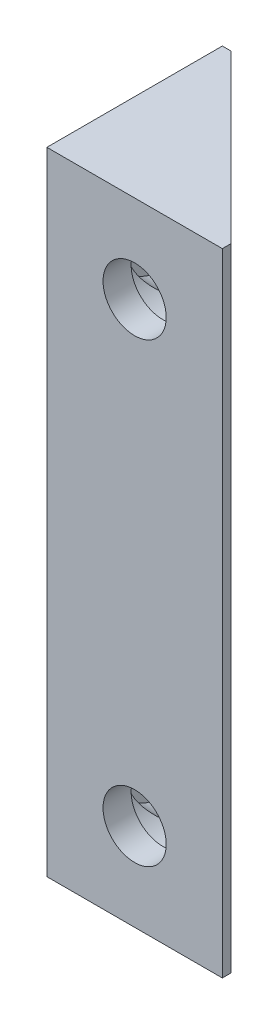
SolidWorks part; units mm, degrees
ref_plane "Front Plane" through (0, 0, 0) normal (0, 0, 1) x (1, 0, 0)
ref_plane "Top Plane" through (0, 0, 0) normal (0, 1, 0) x (1, 0, 0)
ref_plane "Right Plane" through (0, 0, 0) normal (1, 0, 0) x (0, 0, -1)
sketch "Sketch2" plane through (0, 0, 0) normal (0, 1, 0) x (1, 0, 0)
  line L0 (0, 0) -> (0, 20)
  line L2 (20, 0) -> (0, 0)
  line L3 (0, 20) -> (1, 20)
  line L4 (20, 0) -> (20, 1)
  line L5 (1, 20) -> (20, 1)
  dimension "D1" = 20
  dimension "D2" = 1
extrude "Boss-Extrude1" add sketch "Sketch2" along normal mid plane 72
sketch "Sketch3" plane through (0, 0, 0) normal (0, 0, 1) x (1, 0, 0)
  line L0 (0, 36) -> (20, 36) construction
  line L1 (0, 36) -> (0, -36) construction
  line L2 (11, 0) -> (-11, 0) construction
  circle A0 centre (10, 26) radius 3.6
  circle A1 centre (10, 26) radius 5.5
  circle A2 centre (10, -26) radius 3.6
  circle A3 centre (10, -26) radius 5.5
  dimension "D1" = 7.2
  dimension "D2" = 11
  dimension "D3" = 10
  dimension "D4" = 10
extrude "Cut-Extrude1" cut sketch "Sketch3" against normal up to surface (7.4 mm away) contours A0 | A2 region at (10, 26, 0) up to face at (10.5, 0, -10.5)
extrude "Cut-Extrude3" cut sketch "Sketch3<4>" against normal up to surface (11.4 mm away) from offset 3.2 up to face at (10.5, 0, -10.5) offset against normal yes
sketch "Sketch3<4>" plane through (0, 0, 0) normal (0, 0, 1) x (1, 0, 0) same geometry as "Sketch3"
sketch "Sketch4" plane through (0, 0, 0) normal (-1, 0, 0) x (0, 0, 1)
  line L0 (-20, 36) -> (0, 36) construction
  line L1 (0, 36) -> (0, -36) construction
  line L2 (11, 0) -> (-11, 0) construction
  circle A0 centre (-10, 26) radius 3.6
  circle A1 centre (-10, 26) radius 5.5
  circle A2 centre (-10, -26) radius 3.6
  circle A3 centre (-10, -26) radius 5.5
  dimension "D1" = 7.2
  dimension "D2" = 11
  dimension "D3" = 10
  dimension "D4" = 10
extrude "Cut-Extrude2" cut sketch "Sketch4" against normal up to surface (14.6 mm away) contours A0 | A2 region at (0, 26, -10) region at (0, -26, -10) up to face at (15.5, 26, -5.5)
extrude "Cut-Extrude4" cut sketch "Sketch4<3>" against normal up to surface (11.4 mm away) from offset 3.2 up to face at (15.5, 26, -5.5) offset against normal yes
sketch "Sketch4<3>" plane through (0, 0, 0) normal (-1, 0, 0) x (0, 0, 1) same geometry as "Sketch4"
